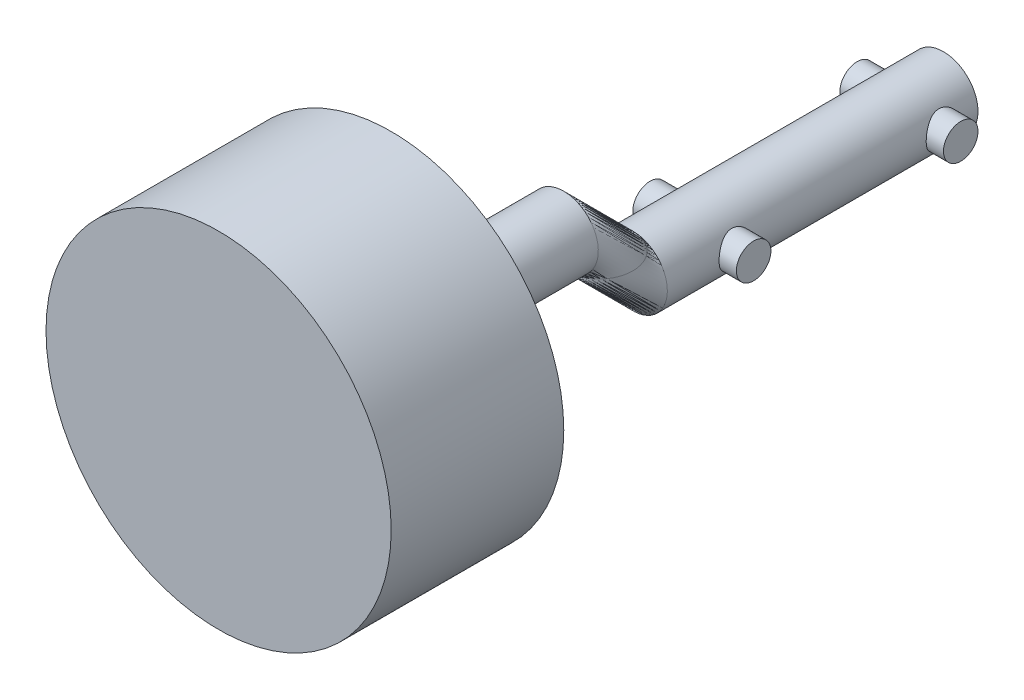
SolidWorks part; units mm, degrees
ref_plane "Plan de face" through (0, 0, 0) normal (0, 0, 1) x (1, 0, 0)
ref_plane "Plan de dessus" through (0, 0, 0) normal (0, 1, 0) x (1, 0, 0)
ref_plane "Plan de droite" through (0, 0, 0) normal (1, 0, 0) x (0, 0, -1)
sketch "Esquisse1" plane through (0, 0, 0) normal (0, 0, 1) x (1, 0, 0)
  circle A0 centre (0, 0) radius 10
  dimension "D1" = 20
extrude "Boss.-Extru.1" add sketch "Esquisse1" along normal blind 10
sketch "Esquisse2" plane through (0, 0, 0) normal (0, 0, -1) x (-1, 0, 0)
  circle A0 centre (0, 0) radius 2
  dimension "D1" = 4
sketch "Esquisse3" plane through (0, 0, 0) normal (1, 0, 0) x (0, 0, -1)
  line L0 (0, 0) -> (10, 0)
  line L1 (14, -4) -> (32, -4)
  line L2 (10, -2) -> (21.167, -2) construction
  arc A0 (10, 0) -> (12, -2) centre (10, -2) cw
  arc A1 (12, -2) -> (14, -4) centre (14, -2) ccw
  point P7 (9.3596, -1.8947)
  point P10 (0, 0)
  point P11 (23.6974, -3.977)
  dimension "D2" = 2
  dimension "D3" = 2
  dimension "D1" = 10
  dimension "D4" = 18
sweep "Balayage1" add profiles "Esquisse2" path "Esquisse3"
sketch "Esquisse4" plane through (0, 0, 0) normal (1, 0, 0) x (0, 0, -1)
  line L0 (12.7428, -4) -> (30.7185, -4) construction
  line L1 (32, -6) -> (32, -2) construction
  circle A0 centre (18, -4) radius 1
  circle A1 centre (30, -4) radius 1
  point P6 (0, 0)
  point P8 (0, 0)
  point P11 (0, 0)
  dimension "D1" = 2
  dimension "D2" = 2
  dimension "D3" = 4
  dimension "D4" = 12
  dimension "D5" = 2
extrude "Boss.-Extru.2" add sketch "Esquisse4" along normal blind 3 and the other way blind 3
